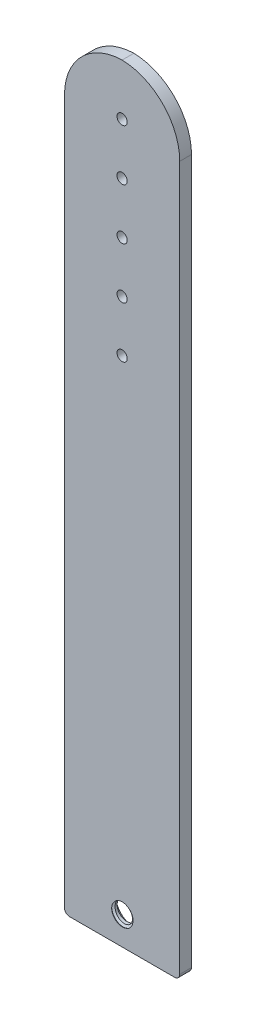
SolidWorks part; units mm, degrees
material "Black Leather"
ref_plane "Front Plane" through (0, 0, 0) normal (0, 0, 1) x (1, 0, 0)
ref_plane "Top Plane" through (0, 0, 0) normal (0, 1, 0) x (1, 0, 0)
ref_plane "Right Plane" through (0, 0, 0) normal (1, 0, 0) x (0, 0, -1)
sketch "Sketch1" plane through (0, 0, 0) normal (0, 0, 1) x (1, 0, 0)
  line L1 (-11.25, 0) -> (11.25, 0)
  line L2 (-11.25, 0) -> (-11.25, 150)
  line L3 (-11.25, 150) -> (11.25, 150)
  line L4 (11.25, 0) -> (11.25, 150)
  circle A0 centre (0, 140) radius 1
  circle A1 centre (0, 130) radius 1
  circle A2 centre (0, 120) radius 1
  circle A3 centre (0, 110) radius 1
  circle A4 centre (0, 100) radius 1
  point P4 (0, 0)
  dimension "D3" = 2
  dimension "L_footStrap" = 150
  dimension "width_strap" = 22.5
  dimension "D4" = 10
  dimension "D5" = 5
extrude "Boss-Extrude1" add sketch "Sketch1" along normal blind 2.3
fillet "Fillet1" radius 11.5 2 edges at (11.25, 150, 1.15) (-11.25, 150, 1.15)
hole_wizard "CSK for #6 Flat Head Machine Screw (100)1" positions "Sketch2" profile "Sketch3" countersink size "#6" standard "ANSI Inch" end condition up to next
sketch "Sketch2" plane through (0, 0, 0) normal (0, 0, -1) x (-1, 0, 0)
  line L0 (11.25, 138.5) -> (11.25, 0) construction
  line L1 (11.25, 0) -> (-11.25, 0) construction
  point P0 (0, 5.75)
  dimension "D1" = 11.25
  dimension "D2" = 5.75
sketch "Sketch3" plane through (0, 5.75, 0) normal (1, 0, 0) x (0, 1, 0)
  line L0 (0, 0) -> (0, 2.3)
  line L1 (0, 2.3) -> (1.8986, 2.3)
  line L2 (1.8986, 2.3) -> (1.8986, 1.38)
  line L3 (1.8986, 1.38) -> (3.5433, 0)
  line L5 (3.5433, 0) -> (0, 0)
  line L6 (-1.8987, 1.38) -> (-3.5433, 0) construction
  line L11 (0, -6.35) -> (0, 107.95) construction
  dimension "Thru Hole Dia." = 3.7973
  dimension "Thru Hole Depth" = 2.3
  dimension "Near C'Sink Dia." = 7.0866
  dimension "Near C'Sink Angle" = 100
thread "Thread1" pitch 0.7937 method cut profile "Thread Profile1" start angle 0, offset 0, length 0, pitch 0.7937, diameter 3.7973
ref_plane "Plane1" through (1.8986, 5.75, 1.38) normal (0, -1, 0) x (1, 0, 0)
sketch "Thread Profile1" plane through (1.8986, 5.75, 1.38) normal (0, -1, 0) x (1, 0, 0)
  line L0 (0, 0) -> (0, 0.7937) construction
  line L1 (0, 0) -> (0.4296, 0.248)
  line L2 (0.4296, 0.248) -> (0.4296, 0.3473)
  line L3 (0.4296, 0.3473) -> (0, 0.5953)
  line L4 (0.4296, 0.2977) -> (0, 0.2977) construction
  line L11 (0, 0) -> (0, 0.5953)
  point P2 (0, 0)
  dimension "Pitch" = 0.7937
  dimension "Profile_Angle" = 60
  dimension "Profile_Land" = 0.0992
  dimension "Profile_Height" = 0.4296
fillet "Fillet2" radius 1 2 edges at (-11.25, 0, 1.15) (11.25, 0, 1.15)
equation "\"CBoot_L_nominal\"= 0.0135m"
equation "\"D2@Sketch2\"=(\"CBoot_L_nominal\"/2)-0.001m"
